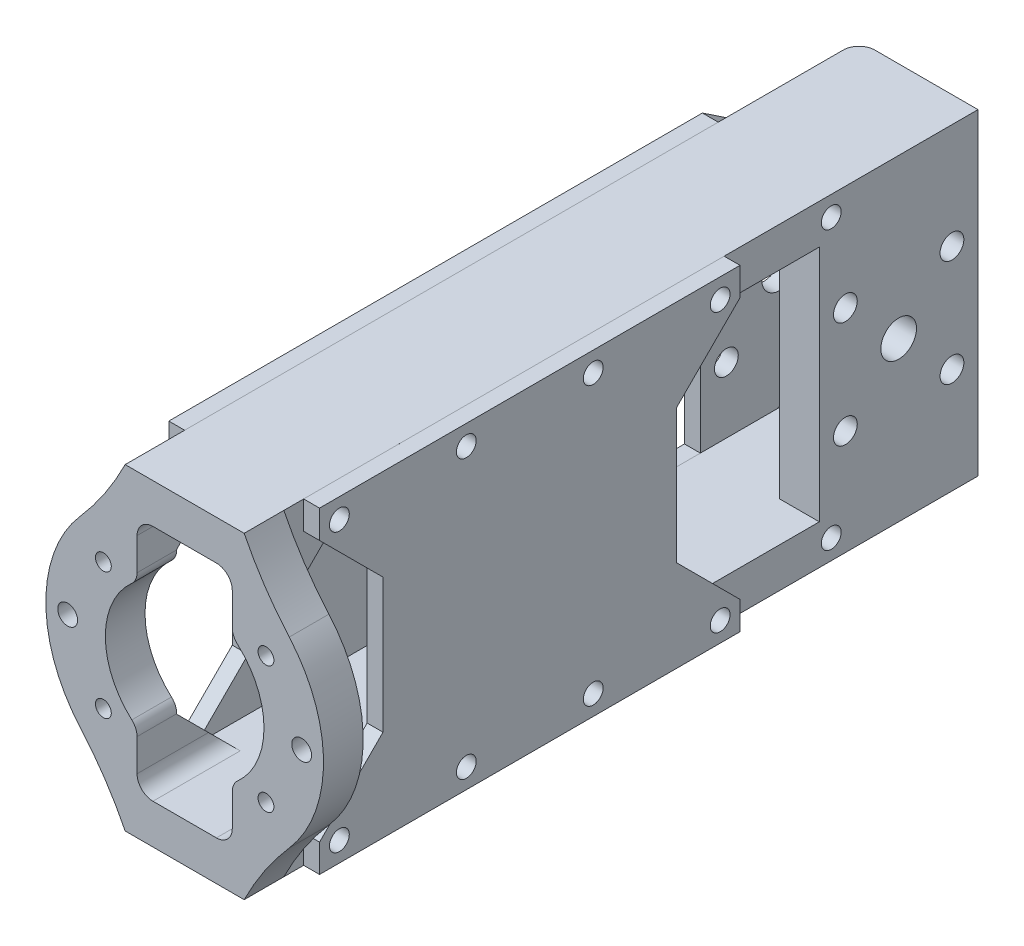
SolidWorks part; units mm, degrees
material "ABS"
ref_plane "前视基准面" through (0, 0, 0) normal (0, 0, 1) x (1, 0, 0)
ref_plane "上视基准面" through (0, 0, 0) normal (0, 1, 0) x (1, 0, 0)
ref_plane "右视基准面" through (0, 0, 0) normal (1, 0, 0) x (0, 0, -1)
sketch "草图1" plane through (0, 0, 0) normal (0, 0, 1) x (1, 0, 0)
  line L0 (19.25, 0) -> (-19.25, 0) construction
  line L1 (0, -27.5) -> (0, 27.5) construction
  line L2 (-7.5, 15.8114) -> (-7.5, 20)
  line L3 (7.5, 15.8114) -> (7.5, 20)
  line L6 (-7.5, 20) -> (7.5, 20)
  line L7 (-7.5, -20) -> (7.5, -20)
  line L8 (7.5, -15.8114) -> (7.5, -20)
  line L9 (-7.5, -15.8114) -> (-7.5, -20)
  circle A0 centre (-10.25, 8) radius 1
  circle A1 centre (-14.75, 0) radius 1.25
  circle A2 centre (-10.25, -8) radius 1
  circle A3 centre (10.25, -8) radius 1
  circle A4 centre (14.75, 0) radius 1.25
  circle A5 centre (10.25, 8) radius 1
  circle A6 centre (0, 0) radius 10
  circle A7 centre (0, 0) radius 17.5
  dimension "D1" = 29.5
  dimension "D2" = 20.5
  dimension "D3" = 16
  dimension "D4" = 2
  dimension "D5" = 2.5
  dimension "D7" = 20
  dimension "D8" = 3.0024
  dimension "D9" = 35
  dimension "D10" = 15
  dimension "D11" = 20
extrude "凸台-拉伸1" add sketch "草图1" along normal blind 5 contours A7 A6 A5 A2 A1 A0 A3 A4 | A7 L3 L6 L2 | A7 L9 L7 L8 region at (0, 18.4333, 0) region at (0, 17.005, 0) region at (0, -18.4333, 0)
sketch "草图3" plane through (0, 0, 0) normal (1, 0, 0) x (0, 0, -1)
  line L0 (0, 20) -> (87.5, 20)
  line L1 (87.5, 20) -> (87.5, 15)
  line L2 (87.5, 15) -> (6, 15)
  line L3 (6, 15) -> (0, 9)
  line L4 (0, 15.8114) -> (0, 20) construction
  line L5 (0, 20) -> (0, 9)
  dimension "D1" = 5
  dimension "D2" = 45
  dimension "D3" = 6
  dimension "D4" = 87.5
extrude "凸台-拉伸2" add sketch "草图3" along normal mid plane 15
mirror "镜向2" about plane through (0, 0, 0) normal (0, 1, 0) of "凸台-拉伸2"
fillet "圆角2" radius 40 4 edges at (-7.5, 15.8114, 2.5) (7.5, 15.8114, 2.5) (-7.5, -15.8114, 2.5) (7.5, -15.8114, 2.5)
sketch "草图9" plane through (0, 0, 5) normal (0, 0, 1) x (1, 0, 0)
  line L0 (-6, 15) -> (6, 15)
  line L2 (-6, 8) -> (6, 8)
  line L3 (-6, 8) -> (-6, 15)
  line L5 (6, 8) -> (6, 15)
  line L11 (19.25, 0) -> (-19.25, 0) construction
  line L12 (6, -8) -> (6, -15)
  line L13 (-6, -8) -> (-6, -15)
  line L14 (-6, -8) -> (6, -8)
  line L15 (-6, -15) -> (6, -15)
  circle A1 centre (0, 0) radius 10 construction
  dimension "D2" = 12
  dimension "D4" = 7
extrude "切除-拉伸2" cut sketch "草图9" against normal blind 45
fillet "圆角1" radius 2 10 edges at (-7.5, 17.5, -87.5) (-6, 8, 2.5) (6, 8, 2.5) (-7.5, -17.5, -87.5) (6, -8, 2.5) (6, 15, -0.5) (-6, 15, -0.5) (-6, -15, -0.5) (6, -15, -0.5) (-6, -8, 2.5)
sketch "草图10" plane through (0, 0, 0) normal (1, 0, 0) x (0, 0, -1)
  line L0 (6, -15) -> (87.5, -15) construction
  line L1 (87.5, 15) -> (67.5, 15)
  line L2 (87.5, 15) -> (87.5, -15)
  line L3 (87.5, -15) -> (67.5, -15)
  line L4 (67.5, 15) -> (67.5, -15)
  circle A0 centre (77.5, 0) radius 9.5 construction
  circle A1 centre (84.2175, 6.7175) radius 1.5
  circle A2 centre (84.2175, -6.7175) radius 1.5
  circle A3 centre (70.7825, -6.7175) radius 1.5
  circle A4 centre (70.7825, 6.7175) radius 1.5
  circle A5 centre (77.5, 0) radius 2.25
  point P11 (0, 0)
  point P20 (77.5, 0)
  point P22 (77.5, 15)
  dimension "D2" = 3
  dimension "D3" = 19
  dimension "D6" = 4.5
  dimension "D4" = 77.5
  dimension "D5" = 3.2825
  dimension "D1" = 4
extrude "凸台-拉伸3" add sketch "草图10" against normal blind 5 from surface starting at face at (7.5, 15.8, -36.2)
sketch "草图12" plane through (-7.5, 0, 0) normal (-1, 0, 0) x (0, 0, 1)
  line L0 (0, 20) -> (-85.5, 20) construction
  line L2 (0, 20) -> (0, 11.5107) construction
  line L3 (19.25, 0) -> (-19.25, 0) construction
  circle A0 centre (-5, 17.5) radius 1.25
  circle A1 centre (-21, 17.5) radius 1.25
  circle A2 centre (-37, 17.5) radius 1.25
  circle A3 centre (-53, 17.5) radius 1.25
  circle A4 centre (-69, 17.5) radius 1.25
  circle A5 centre (-69, -17.5) radius 1.25
  circle A6 centre (-53, -17.5) radius 1.25
  circle A7 centre (-37, -17.5) radius 1.25
  circle A8 centre (-21, -17.5) radius 1.25
  circle A9 centre (-5, -17.5) radius 1.25
  dimension "D1" = 2.5
  dimension "D2" = 2.5
  dimension "D4" = 5
  dimension "D5" = 16
  dimension "D3" = 5
extrude "切除-拉伸3" cut sketch "草图12" against normal through all both and the other way through all
sketch "草图13" plane through (7.5, 0, 0) normal (1, 0, 0) x (0, 0, -1)
  line L0 (0, 20) -> (87.5, 20) construction
  line L1 (2.5, 20) -> (55.5, 20)
  line L2 (2.5, 20) -> (2.5, 16.4645)
  line L3 (2.5, -20) -> (55.5, -20)
  line L4 (55.5, 20) -> (55.5, 16.4645)
  line L5 (0, -20) -> (87.5, -20) construction
  line L6 (29, 20) -> (29, -20) construction
  line L7 (2.5, 16.4645) -> (10.5, 8.4645)
  line L8 (10.5, 8.4645) -> (10.5, -8.4645)
  line L9 (19.25, 0) -> (-19.25, 0) construction
  line L10 (2.5, -16.4645) -> (10.5, -8.4645)
  line L11 (2.5, -16.4645) -> (2.5, -20)
  line L12 (55.5, -16.4645) -> (47.5, -8.4645)
  line L13 (47.5, 8.4645) -> (47.5, -8.4645)
  line L14 (55.5, 16.4645) -> (47.5, 8.4645)
  line L15 (55.5, -16.4645) -> (55.5, -20)
  circle A0 centre (5, 17.5) radius 1.25 construction
  circle A1 centre (53, 17.5) radius 1.25 construction
  circle A2 centre (21, 17.5) radius 1.25 construction
  circle A3 centre (37, 17.5) radius 1.25 construction
  circle A4 centre (53, -17.5) radius 1.25 construction
  circle A5 centre (37, -17.5) radius 1.25 construction
  circle A6 centre (21, -17.5) radius 1.25 construction
  circle A7 centre (5, -17.5) radius 1.25 construction
  circle A8 centre (5, 17.5) radius 1.25
  circle A9 centre (21, 17.5) radius 1.25
  circle A10 centre (37, 17.5) radius 1.25
  circle A11 centre (53, 17.5) radius 1.25
  circle A12 centre (53, -17.5) radius 1.25
  circle A13 centre (37, -17.5) radius 1.25
  circle A14 centre (21, -17.5) radius 1.25
  circle A15 centre (5, -17.5) radius 1.25
  point P19 (10.835, -5.518)
  dimension "D1" = 2.5
  dimension "D2" = 2.5
  dimension "D3" = 8
  dimension "D4" = 45
  dimension "D5" = 2.5
extrude "凸台-拉伸4" add sketch "草图13" along normal blind 2 separate body
sketch "草图14" plane through (0, 0, 0) normal (1, 0, 0) x (0, 0, -1)
  line L0 (0, -20) -> (85.5, -20) construction
  line L1 (69.7592, 20) -> (2.5, 20)
  line L2 (87.5, 8.1309) -> (87.5, -8.1309)
  line L3 (69.7592, -20) -> (2.5, -20)
  line L4 (2.5, 20) -> (2.5, 16.4645)
  line L5 (87.5, -8.1309) -> (69.7592, -20)
  line L6 (10.5, -8.4645) -> (2.5, -16.4645) construction
  line L7 (10.5, 8.4645) -> (10.5, -8.4645) construction
  line L8 (2.5, 16.4645) -> (10.5, 8.4645) construction
  line L9 (10.5, -8.4645) -> (2.5, -16.4645)
  line L10 (10.5, 8.4645) -> (10.5, -8.4645)
  line L11 (2.5, 16.4645) -> (10.5, 8.4645)
  line L12 (2.5, -16.4645) -> (2.5, -20)
  line L13 (55.5, -16.4645) -> (47.5, -8.4645) construction
  line L14 (47.5, -8.4645) -> (47.5, 8.4645) construction
  line L15 (47.5, 8.4645) -> (55.5, 16.4645) construction
  line L16 (54.0355, -15) -> (47.5, -8.4645)
  line L17 (47.5, -8.4645) -> (47.5, 8.4645)
  line L18 (47.5, 8.4645) -> (54.0355, 15)
  line L19 (67.5, 15) -> (54.0355, 15)
  line L20 (6, 15) -> (85.5, 15) construction
  line L21 (67.5, 15) -> (67.5, -15)
  line L22 (6, -15) -> (85.5, -15) construction
  line L23 (67.5, -15) -> (54.0355, -15)
  line L24 (19.25, 0) -> (-19.25, 0) construction
  line L25 (87.5, 8.1309) -> (69.7592, 20)
  line L26 (87.5, -15) -> (87.5, 15) construction
  circle A0 centre (69, 17.5) radius 1.25 construction
  circle A1 centre (69, -17.5) radius 1.25 construction
  circle A2 centre (84.2175, -6.7175) radius 1.5 construction
  circle A3 centre (53, 17.5) radius 1.25 construction
  circle A4 centre (37, 17.5) radius 1.25 construction
  circle A5 centre (21, 17.5) radius 1.25 construction
  circle A6 centre (5, 17.5) radius 1.25 construction
  circle A7 centre (5, -17.5) radius 1.25 construction
  circle A8 centre (21, -17.5) radius 1.25 construction
  circle A9 centre (37, -17.5) radius 1.25 construction
  circle A10 centre (53, -17.5) radius 1.25 construction
  circle A11 centre (84.2175, 6.7175) radius 1.5 construction
  circle A12 centre (70.7825, 6.7175) radius 1.5 construction
  circle A13 centre (77.5, 0) radius 2.25 construction
  circle A14 centre (70.7825, -6.7175) radius 1.5 construction
  circle A15 centre (84.2175, -6.7175) radius 1.5
  circle A16 centre (84.2175, 6.7175) radius 1.5
  circle A17 centre (70.7825, 6.7175) radius 1.5
  circle A18 centre (77.5, 0) radius 2.25
  circle A19 centre (70.7825, -6.7175) radius 1.5
  circle A20 centre (69, -17.5) radius 1.25
  circle A21 centre (53, -17.5) radius 1.25
  circle A22 centre (37, -17.5) radius 1.25
  circle A23 centre (21, -17.5) radius 1.25
  circle A24 centre (5, -17.5) radius 1.25
  circle A25 centre (5, 17.5) radius 1.25
  circle A26 centre (21, 17.5) radius 1.25
  circle A27 centre (37, 17.5) radius 1.25
  circle A28 centre (53, 17.5) radius 1.25
  circle A29 centre (69, 17.5) radius 1.25
  point P0 (84.8838, 9.8812)
  dimension "D2" = 2.5
  dimension "D3" = 3
extrude "凸台-拉伸5" add sketch "草图14" against normal blind 2 from surface separate body starting at face at (-7.5, 16.25, -69)
